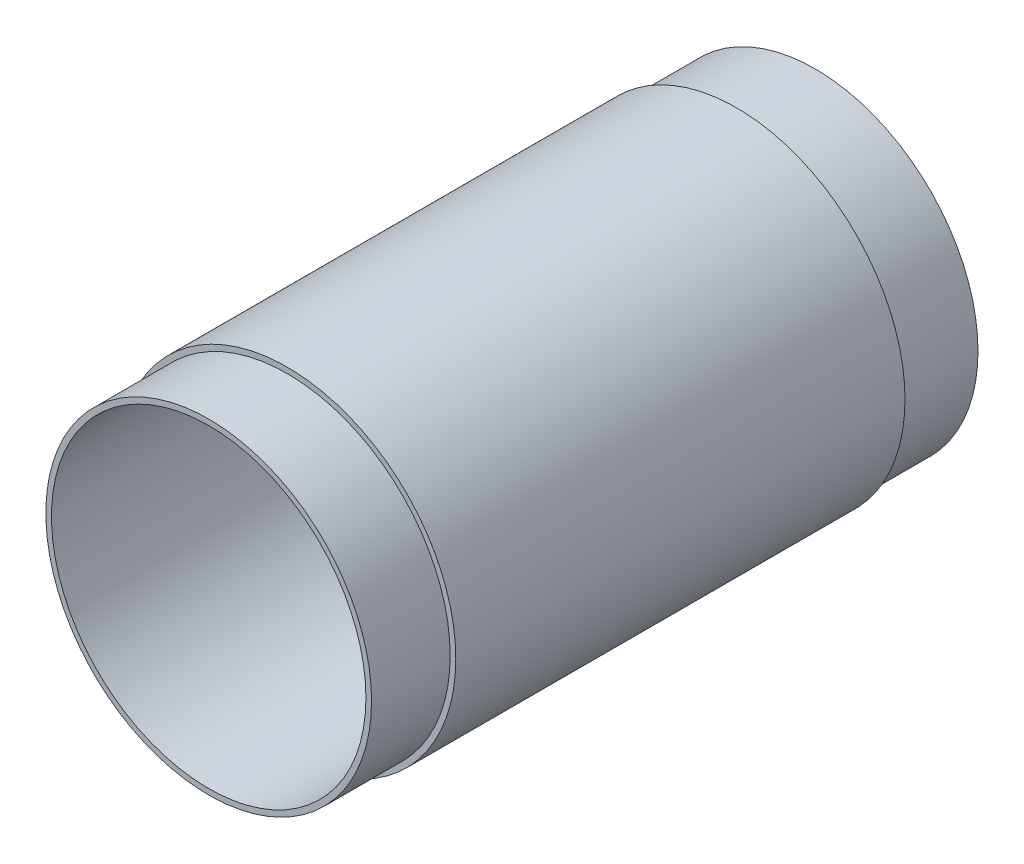
SolidWorks part; units mm, degrees
material "1060 Alloy"
ref_plane "Front Plane" through (0, 0, 0) normal (0, 0, 1) x (1, 0, 0)
ref_plane "Top Plane" through (0, 0, 0) normal (0, 1, 0) x (1, 0, 0)
ref_plane "Right Plane" through (0, 0, 0) normal (1, 0, 0) x (0, 0, -1)
sketch "Sketch1" plane through (0, 0, 0) normal (1, 0, 0) x (0, 0, -1)
  line L0 (0, 14) -> (54, 14)
  line L1 (54, 14) -> (54, 14.5)
  line L2 (54, 14.5) -> (47, 14.5)
  line L3 (47, 14.5) -> (47, 15)
  line L4 (47, 15) -> (7, 15)
  line L5 (7, 15) -> (7, 14.5)
  line L6 (7, 14.5) -> (0, 14.5)
  line L7 (0, 14.5) -> (0, 14)
  line L8 (0, 0) -> (54, 0) construction
  dimension "D1" = 54
  dimension "D2" = 14
  dimension "D3" = 1
  dimension "D4" = 0.5
  dimension "D5" = 7
revolve "Revolve1" add sketch "Sketch1" angle 360 about L8
